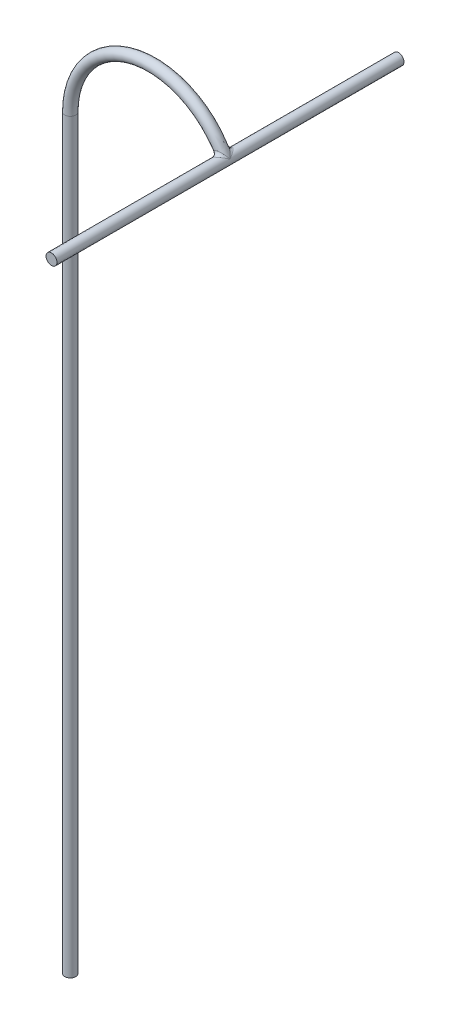
SolidWorks part; units mm, degrees
ref_plane "Front Plane" through (0, 0, 0) normal (0, 0, 1) x (1, 0, 0)
ref_plane "Top Plane" through (0, 0, 0) normal (0, 1, 0) x (1, 0, 0)
ref_plane "Right Plane" through (0, 0, 0) normal (1, 0, 0) x (0, 0, -1)
sketch "Sketch1" plane through (0, 0, 0) normal (0, 0, 1) x (1, 0, 0)
  circle A0 centre (0, 0) radius 15
  dimension "D1" = 30
extrude "Boss-Extrude1" add sketch "Sketch1" along normal blind 950 contours A0
ref_plane "Plane1" through (0, 0, 475) normal (0, 0, 1) x (1, 0, 0)
sketch "Sketch2" plane through (0, 0, 475) normal (0, 0, 1) x (1, 0, 0)
  line L0 (0, 0) -> (0, -100) construction
  line L1 (0, -100) -> (-200, -100) construction
  line L2 (-200, -100) -> (-423.6068, -100) construction
  line L3 (-423.6068, -100) -> (-423.6068, -2143)
  arc A0 (0, 0) -> (-423.6068, -100) centre (-200, -100) ccw
sweep "Sweep1" add path "Sketch2" circular profile diameter 30 parameters "D3"=30
fillet "Fillet1" radius 10 2 edges at (-5.9601, 13.7651, 489.9414) (-8.0386, 12.6642, 460.0351)
